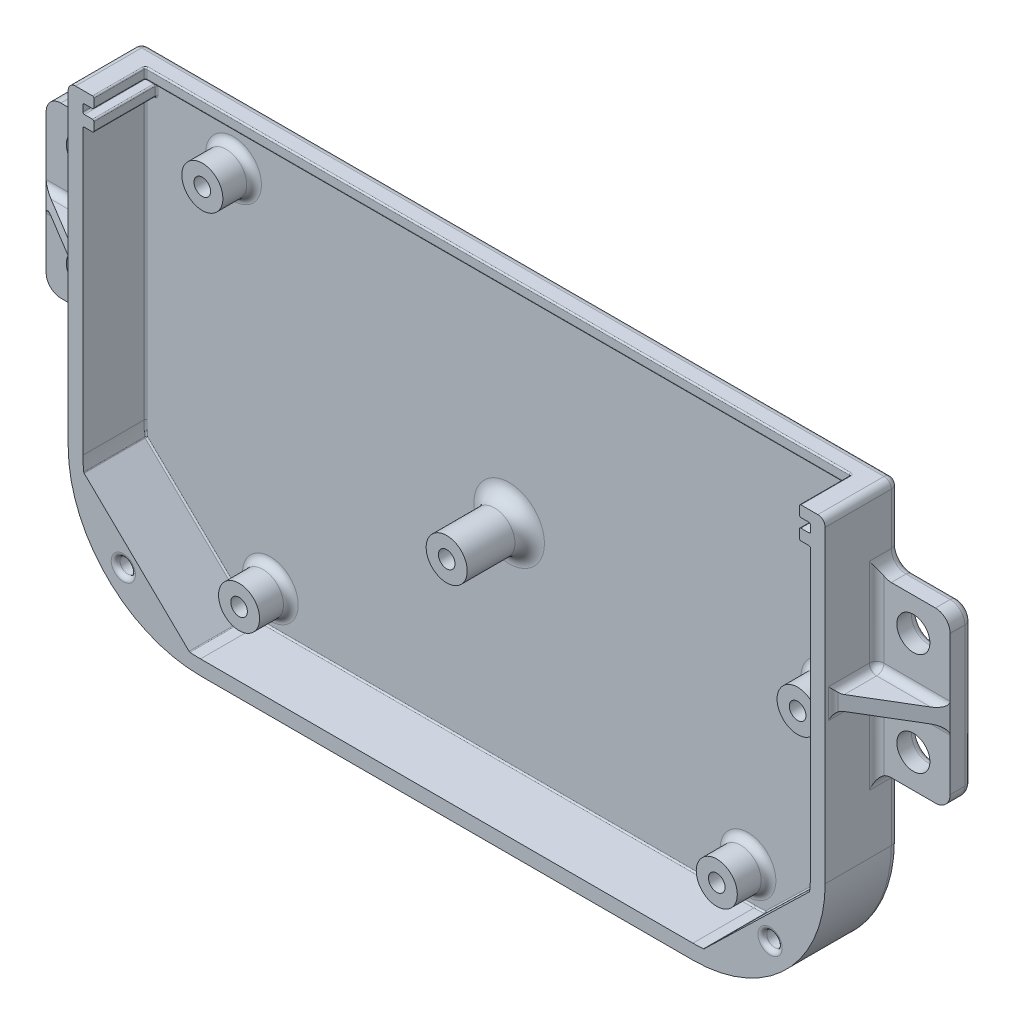
SolidWorks part; units mm, degrees
ref_plane "Plan de face" through (0, 0, 0) normal (0, 0, 1) x (1, 0, 0)
ref_plane "Plan de dessus" through (0, 0, 0) normal (0, 1, 0) x (1, 0, 0)
ref_plane "Plan de droite" through (0, 0, 0) normal (1, 0, 0) x (0, 0, -1)
sketch "Esquisse1" plane through (0, 0, 0) normal (0, 0, 1) x (1, 0, 0)
  line L1 (-50, -0.5) -> (50, -0.5) construction
  line L2 (-50, -0.5) -> (-50, 0.5) construction
  line L3 (-50, 0.5) -> (50, 0.5) construction
  line L4 (50, -0.5) -> (50, 0.5) construction
  line L5 (-50, -0.5) -> (50, 0.5) construction
  line L6 (-50, 0.5) -> (50, -0.5) construction
  line L7 (-51.5, 2) -> (51.5, 2)
  line L8 (-51.5, 2) -> (-51.5, -41)
  line L9 (-33.5, -59) -> (33.5, -59)
  line L10 (51.5, 2) -> (51.5, -41)
  arc A0 (51.5, -41) -> (33.5, -59) centre (33.5, -41) cw
  arc A1 (-33.5, -59) -> (-51.5, -41) centre (-33.5, -41) cw
  point P0 (0, 0)
  point P10 (0, 2)
  point P15 (-51.5, -59)
  dimension "D6" = 18
  dimension "D1" = 100
  dimension "D2" = 1
  dimension "D3" = 1.5
  dimension "D4" = 1.5
  dimension "D5" = 61
extrude "Boss.-Extru.1" add sketch "Esquisse1" along normal blind 10
sketch "Esquisse2" plane through (0, 0, 10) normal (0, 0, 1) x (1, 0, 0)
  line L3 (51.5, 2) -> (-51.5, 2) construction
  line L4 (-49.5, 2) -> (49.5, 2)
  line L6 (49.5, -41) -> (49.5, 2)
  line L7 (-33.5, -57) -> (33.5, -57)
  line L8 (-49.5, 2) -> (-49.5, -41)
  line L9 (49.5, -41) -> (49.5, 2)
  line L10 (-33.5, -57) -> (33.5, -57)
  line L11 (-49.5, 2) -> (-49.5, -41)
  arc A4 (33.5, -57) -> (49.5, -41) centre (33.5, -41) ccw
  arc A5 (-49.5, -41) -> (-33.5, -57) centre (-33.5, -41) ccw
  arc A6 (33.5, -57) -> (49.5, -41) centre (33.5, -41) ccw
  arc A7 (-49.5, -41) -> (-33.5, -57) centre (-33.5, -41) ccw
  dimension "D2" = 0
  dimension "D1" = 2
extrude "Enlèv. mat.-Extru.1" cut sketch "Esquisse2" against normal offset from surface (8.5 mm away) 1.5 up to face at (0, -33.9093, 0)
sketch "Esquisse3" plane through (0, 0, 1.5) normal (0, 0, 1) x (1, 0, 0)
  line L0 (49.5, -41) -> (49.5, 2) construction
  line L1 (-49.5, 2) -> (49.5, 2)
  line L2 (-49.5, 2) -> (-49.5, 0.5)
  line L3 (-49.5, 0.5) -> (49.5, 0.5)
  line L4 (49.5, 2) -> (49.5, 0.5)
  dimension "D1" = 1.5
extrude "Boss.-Extru.2" add sketch "Esquisse3" along normal blind 1.5
sketch "Esquisse4" plane through (0, 0, 1.5) normal (0, 0, 1) x (1, 0, 0)
  line L0 (-49.5, 0.5) -> (-49.5, -41) construction
  line L1 (-49.5, -0.75) -> (-48, -0.75)
  line L2 (-49.5, -0.75) -> (-49.5, -2.25)
  line L3 (-49.5, -2.25) -> (-48, -2.25)
  line L4 (-48, -0.75) -> (-48, -2.25)
  line L5 (49.5, -41) -> (49.5, 2) construction
  line L6 (49.5, -0.75) -> (48, -0.75)
  line L7 (49.5, -0.75) -> (49.5, -2.25)
  line L8 (49.5, -2.25) -> (48, -2.25)
  line L9 (48, -0.75) -> (48, -2.25)
  line L10 (-49.5, 0.5) -> (49.5, 0.5) construction
  line L11 (49.5, 2) -> (48, 2)
  line L12 (49.5, 2) -> (49.5, 0.5)
  line L13 (49.5, 0.5) -> (48, 0.5)
  line L14 (48, 2) -> (48, 0.5)
  line L16 (-49.5, 2) -> (-48, 2)
  line L17 (-49.5, 2) -> (-49.5, 0.5)
  line L18 (-49.5, 0.5) -> (-48, 0.5)
  line L19 (-48, 2) -> (-48, 0.5)
  dimension "D1" = 1.5
  dimension "D2" = 1.5
  dimension "D3" = 1.25
  dimension "D4" = 1.5
extrude "Boss.-Extru.3" add sketch "Esquisse4" along normal up to surface (8.5 mm away) up to face at (0, -33.5069, 10)
sketch "Esquisse5" plane through (0, 0, 0) normal (0, 0, -1) x (-1, 0, 0)
  line L0 (-51.5, -41) -> (-51.5, 2) construction
  line L1 (-51.5, -10) -> (-59.5, -10)
  line L2 (-51.5, -10) -> (-51.5, -35)
  line L3 (-51.5, -35) -> (-59.5, -35)
  line L4 (-59.5, -10) -> (-59.5, -35)
  line L6 (0, 0) -> (0, -67.9713) construction
  line L7 (-51.5, 2) -> (51.5, 2) construction
  line L11 (51.5, -35) -> (59.5, -35)
  line L12 (51.5, -10) -> (51.5, -35)
  line L13 (51.5, -10) -> (59.5, -10)
  line L14 (59.5, -10) -> (59.5, -35)
  line L15 (-55.5, -10) -> (-55.5, -35) construction
  circle A0 centre (-55.5, -15) radius 2.25
  circle A1 centre (-55.5, -30) radius 2.25
  circle A2 centre (55.5, -15) radius 2.25
  circle A3 centre (55.5, -30) radius 2.25
  point P8 (-59.5, -22.5)
  point P17 (-51.5, -22.5)
  point P21 (-55.5, -10)
  dimension "D3" = 4.5
  dimension "D4" = 4.5
  dimension "D1" = 8
  dimension "D2" = 25
  dimension "D5" = 7.5
  dimension "D6" = 7.5
  dimension "D7" = 12
extrude "Boss.-Extru.4" [suppressed] add sketch "Esquisse5" against normal blind 3 separate body
fillet "Congé2" [suppressed] radius 2
sketch "Esquisse6" plane through (0, 0, 0) normal (0, 0, -1) x (-1, 0, 0)
  line L0 (-51.5, -41) -> (-51.5, 2) construction
  line L1 (-51.5, -8) -> (-61.5, -8)
  line L2 (-51.5, -8) -> (-51.5, -31)
  line L3 (-51.5, -31) -> (-61.5, -31)
  line L4 (-61.5, -8) -> (-61.5, -31)
  line L5 (-51.5, 2) -> (51.5, 2) construction
  line L6 (0, 0) -> (0, -37.9918) construction
  line L7 (51.5, -8) -> (51.5, -31)
  line L8 (51.5, -31) -> (61.5, -31)
  line L9 (61.5, -8) -> (61.5, -31)
  line L10 (51.5, -8) -> (61.5, -8)
  circle A0 centre (-56.5, -12.5) radius 2.25
  circle A1 centre (-56.5, -26.5) radius 2.25
  circle A2 centre (56.5, -12.5) radius 2.25
  circle A3 centre (56.5, -26.5) radius 2.25
  point P6 (-56.5, -8)
  point P11 (-61.5, -19.5)
  dimension "D5" = 4.5
  dimension "D6" = 4.5
  dimension "D1" = 10
  dimension "D2" = 7
  dimension "D3" = 7
  dimension "D4" = 4.5
  dimension "D7" = 10
extrude "Boss.-Extru.5" add sketch "Esquisse6" against normal blind 3
fillet "Congé3" radius 2 8 edges at (51.5, -8, 1.5) (61.5, -8, 1.5) (51.5, -31, 1.5) (61.5, -31, 1.5) (-51.5, -8, 1.5) (-61.5, -8, 1.5) (-61.5, -31, 1.5) (-51.5, -31, 1.5)
fillet "Congé4" radius 1 26 edges at (-54.25, -12.5, 0) (-54.25, -26.5, 0) (54.25, -12.5, 0) (54.25, -26.5, 0) (52.0858, -7.4142, 0) (51.5, -2, 0) (0, 2, 0) (-51.5, -2, 0) (-52.0858, -7.4142, 0) (-56.5, -8, 0) (-60.9142, -8.5858, 0) (-61.5, -19.5, 0) (-60.9142, -30.4142, 0) (-56.5, -31, 0) (-52.0858, -31.5858, 0) (-51.5, -37, 0) (-46.2279, -53.7279, 0) (0, -59, 0) (46.2279, -53.7279, 0) (51.5, -37, 0) (52.0858, -31.5858, 0) (56.5, -31, 0) (60.9142, -30.4142, 0) (61.5, -19.5, 0) (60.9142, -8.5858, 0) (56.5, -8, 0)
fillet "Congé5" radius 1 6 edges at (-51.2071, 1.7071, 0.2929) (51.2071, 1.7071, 0.2929) (-51.5, 2, 5.5) (51.5, -19.5, 3) (51.5, 2, 5.5) (-51.5, -19.5, 3)
sketch "Esquisse7" plane through (0, 0, 1.5) normal (0, 0, 1) x (1, 0, 0)
  line L0 (59.5, -31) -> (53.5, -31) construction
  line L1 (0, 0) -> (0, -39.8228) construction
  line L2 (-49.3745, -43) -> (-35, -56.9295)
  line L3 (49.3745, -43) -> (35, -56.9295)
  arc A0 (35, -56.9295) -> (49.3745, -43) centre (33.5, -41) ccw
  arc A1 (33.5, -57) -> (49.5, -41) centre (33.5, -41) ccw construction
  arc A2 (33.5, -57) -> (49.5, -41) centre (33.5, -41) ccw construction
  arc A4 (-35, -56.9295) -> (-49.3745, -43) centre (-33.5, -41) cw
  dimension "D1" = 35
  dimension "D2" = 12
  dimension "D3" = 14.3745
extrude "Boss.-Extru.6" add sketch "Esquisse7" along normal up to surface (8.5 mm away) up to face at (0, -15.7565, 10)
sketch "Esquisse8" plane through (0, 0, 10) normal (0, 0, 1) x (1, 0, 0)
  line L0 (-51.5, 1) -> (-51.5, -41) construction
  line L1 (-33.5, -59) -> (33.5, -59) construction
  line L2 (0, 0) -> (0, -39.4098) construction
  circle A0 centre (-44, -51.5) radius 1.05
  circle A1 centre (44, -51.5) radius 1.05
  dimension "D3" = 2.1
  dimension "D1" = 7.5
  dimension "D2" = 7.5
extrude "Enlèv. mat.-Extru.2" cut sketch "Esquisse8" against normal blind 5
fillet "Congé6" [suppressed] radius 1
sketch "Esquisse9" plane through (0, 0, 1.5) normal (0, 0, 1) x (1, 0, 0)
  line L0 (48, 2) -> (-48, 2) construction
  line L1 (0, 2) -> (0, -59) construction
  line L2 (-33.5, -59) -> (33.5, -59) construction
  circle A0 centre (0, -28.5) radius 2.794
  point P8 (0, -28.5)
  dimension "D1" = 5.588
extrude "Boss.-Extru.7" add sketch "Esquisse9" along normal up to surface (8.5 mm away) up to face at (42.95, -51.5, 10)
fillet "Congé7" radius 2 1 edges at (-2.794, -28.5, 1.5)
sketch "Esquisse10" plane through (0, 0, 10) normal (0, 0, 1) x (1, 0, 0)
  circle A0 centre (0, -28.5) radius 0.5
  dimension "D1" = 1
extrude "Enlèv. mat.-Extru.3" cut sketch "Esquisse10" against normal blind 1
sketch "Esquisse11" plane through (0, 0, 1.5) normal (0, 0, 1) x (1, 0, 0)
  circle A0 centre (-37.5, -5.5) radius 2.794
  circle A1 centre (43.5, -26.75) radius 2.794
  circle A2 centre (-32.5, -52.5) radius 2.794
  circle A3 centre (32.5, -52.5) radius 2.794
  circle A4 centre (0, -28.5) radius 0.5 construction
  circle A5 centre (0, -28.5) radius 2.794 construction
  dimension "D1" = 5.588
  dimension "D6" = 43.5
  dimension "D9" = 23
  dimension "D10" = 1.75
  dimension "D11" = 11
  dimension "D8" = 25.75
  dimension "D5" = 37.5
  dimension "D7" = 65
extrude "Boss.-Extru.8" add sketch "Esquisse11" along normal blind 4.25
sketch "Esquisse12" plane through (0, 0, 5.75) normal (0, 0, 1) x (1, 0, 0)
  circle A0 centre (-37.5, -5.5) radius 1.1303
  circle A1 centre (-32.5, -52.5) radius 1.1303
  circle A2 centre (32.5, -52.5) radius 1.1303
  circle A3 centre (43.5, -26.75) radius 1.1303
  dimension "D4" = 2.2606
extrude "Enlèv. mat.-Extru.4" cut sketch "Esquisse12" against normal up to surface (4.25 mm away) up to face at (-35.294, -52.5, 1.5)
fillet "Congé8" radius 1 4 edges at (-35.294, -52.5, 1.5) (29.706, -52.5, 1.5) (40.706, -26.75, 1.5) (-40.294, -5.5, 1.5)
fillet "Congé9" radius 0.6 2 edges at (42.95, -51.5, 10) (-42.95, -51.5, 10)
sketch "Esquisse14" plane through (0, -31, 0) normal (0, -1, 0) x (1, 0, 0)
  line L0 (-61.5, 3) -> (-51.5, 9)
  line L1 (-51.5, 10) -> (-51.5, 1) construction
  line L2 (-51.5, 9) -> (-51.5, 3)
  line L3 (-51.5, 4) -> (-51.5, 1) construction
  line L4 (-51.5, 3) -> (-61.5, 3)
  line L5 (0, 0) -> (0, 19.1691) construction
  line L6 (51.5, 9) -> (51.5, 3)
  line L7 (51.5, 3) -> (61.5, 3)
  line L8 (61.5, 3) -> (51.5, 9)
  dimension "D1" = 6
extrude "Boss.-Extru.9" add sketch "Esquisse14" along normal blind 2 from offset 12 offset against normal yes
fillet "Congé10" radius 1 14 edges at (51.5, -19, 6.5) (51.7929, -19, 3.2929) (51.5, -21, 6.5) (51.7929, -21, 3.2929) (-51.5, -21, 6.5) (-51.7929, -21, 3.2929) (-51.5, -19, 6.5) (-51.7929, -19, 3.2929) (57, -19, 3) (51.5, -20, 9) (57, -21, 3) (-51.5, -20, 9) (-57, -21, 3) (-57, -19, 3)
fillet "Congé11" radius 0.2 38 edges at (48, -1.5, 1.5) (-48, -1.5, 1.5) (49.4686, -42.002, 1.5) (-34.2508, -56.9824, 1.5) (34.2508, -56.9824, 1.5) (-49.4686, -42.002, 1.5) (49.3745, -43, 5.75) (35, -56.9295, 5.75) (-35, -56.9295, 5.75) (-49.3745, -43, 5.75) (48.75, -2.25, 1.5) (48, -2.25, 5.75) (49.5, -2.25, 5.75) (49.5, -21.625, 1.5) (42.1873, -49.9648, 1.5) (0, -57, 1.5) (-42.1873, -49.9648, 1.5) (-48, -2.25, 5.75) (-49.5, -2.25, 5.75) (-49.5, -21.625, 1.5) (-48.75, -2.25, 1.5) (48.75, -0.75, 1.5) (0, 2, 3) (0, 0.5, 3) (48, 1.25, 3) (48, 2, 6.5) (48, 0.5, 6.5) (49.5, 0.5, 5.75) (49.5, -0.75, 5.75) (48, -0.75, 5.75) (-48, 2, 6.5) (-48, 1.25, 3) (-48, 0.5, 6.5) (0, 0.5, 1.5) (-49.5, 0.5, 5.75) (-49.5, -0.75, 5.75) (-48, -0.75, 5.75) (-48.75, -0.75, 1.5)
sketch "Sketch1" plane through (0, 0, 10) normal (0, 0, 1) x (1, 0, 0)
  circle A0 centre (0, -28.5) radius 1.1303
  dimension "D1" = 2.2606
extrude "Cut-Extrude1" cut sketch "Sketch1" against normal up to surface (8.5 mm away) up to face at (-36.294, -52.5, 1.5)
